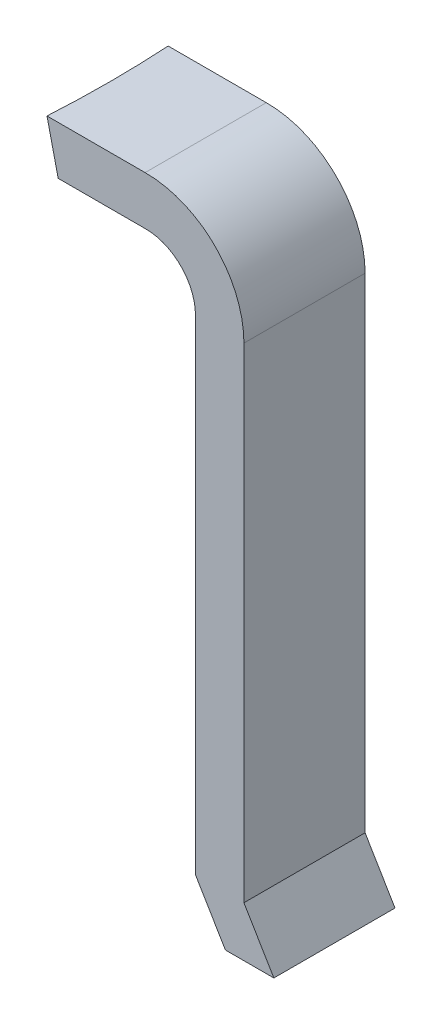
SolidWorks part; units mm, degrees
ref_plane "Front Plane" through (0, 0, 0) normal (0, 0, 1) x (1, 0, 0)
ref_plane "Top Plane" through (0, 0, 0) normal (0, 1, 0) x (1, 0, 0)
ref_plane "Right Plane" through (0, 0, 0) normal (1, 0, 0) x (0, 0, -1)
sketch "Sketch1" plane through (0, 0, 0) normal (0, 0, 1) x (1, 0, 0)
  line L1 (-0.2753, 0.6183) -> (-0.2753, 20.6183)
  line L3 (-4.3535, 22.6748) -> (-4.3535, 24.6748)
  line L4 (-2.2753, 20.6183) -> (-2.2753, 0.6183)
  line L10 (-0.2753, 0.6183) -> (0.9594, -1.4542)
  line L11 (0.9594, -1.4542) -> (-1.0406, -1.4542)
  line L12 (-1.0406, -1.4542) -> (-2.2753, 0.6183)
  arc A1 (-0.2753, 20.6183) -> (-4.3535, 24.6748) centre (-4.3318, 20.6183) ccw
  arc A3 (-2.2753, 20.6183) -> (-4.3535, 22.6748) centre (-4.3318, 20.6183) ccw
  dimension "D2" = 2
  dimension "D1" = 20
  dimension "D3" = 2
  dimension "D5" = 2
extrude "Boss-Extrude1" add sketch "Sketch1" along normal blind 5
sketch "Sketch2" plane through (-4.3535, 0, 0) normal (-1, 0, 0) x (0, 0, 1)
  line L1 (0, 24.6748) -> (5, 24.6748)
  line L2 (0, 24.6748) -> (0, 22.6748)
  line L3 (0, 22.6748) -> (5, 22.6748)
  line L4 (5, 24.6748) -> (5, 22.6748)
extrude "Boss-Extrude2" add sketch "Sketch2" along normal blind 5
sketch "Sketch7" plane through (0, 0, 5) normal (0, 0, 1) x (1, 0, 0)
  line L0 (-9.3535, 24.6748) -> (-8.8917, 22.6748)
  line L1 (-9.3535, 22.6748) -> (-4.3535, 22.6748) construction
  line L2 (-9.3535, 22.6748) -> (-9.3535, 24.6748)
  arc A0 (-8.8917, 22.6748) -> (-9.3535, 22.6748) centre (-9.1226, 23.6748) cw
  dimension "D1" = 13
extrude "Cut-Extrude3" cut sketch "Sketch7" against normal through all
sketch "Sketch8" plane through (0, 0, 5) normal (0, 0, 1) x (1, 0, 0)
  line L5 (-9.1226, 23.6748) -> (-50.5333, 14.1144)
  line L6 (-8.8917, 22.6748) -> (-9.3535, 24.6748) construction
  line L7 (-50.5333, 14.1144) -> (-50.5558, 14.2118)
  line L8 (-50.5558, 14.2118) -> (-9.1451, 23.7722)
  line L9 (-9.1451, 23.7722) -> (-9.1226, 23.6748)
  dimension "D1" = 0.1
  dimension "D2" = 42.5
  dimension "D3" = 90
extrude "Boss-Extrude7" add sketch "Sketch8" against normal through all
sketch "Sketch10" plane through (-5.6733, 24.5738, 0) normal (-0.225, 0.9744, 0) x (0.9744, 0.225, 0)
  line L0 (-3.5631, 0) -> (-3.5631, -5) construction
  circle A0 centre (-45.0631, -2.5) radius 42.5
  dimension "D1" = 41.5
  dimension "D2" = 85
extrude "Cut-Extrude5" cut sketch "Sketch10" against normal blind 2 and the other way blind 2
